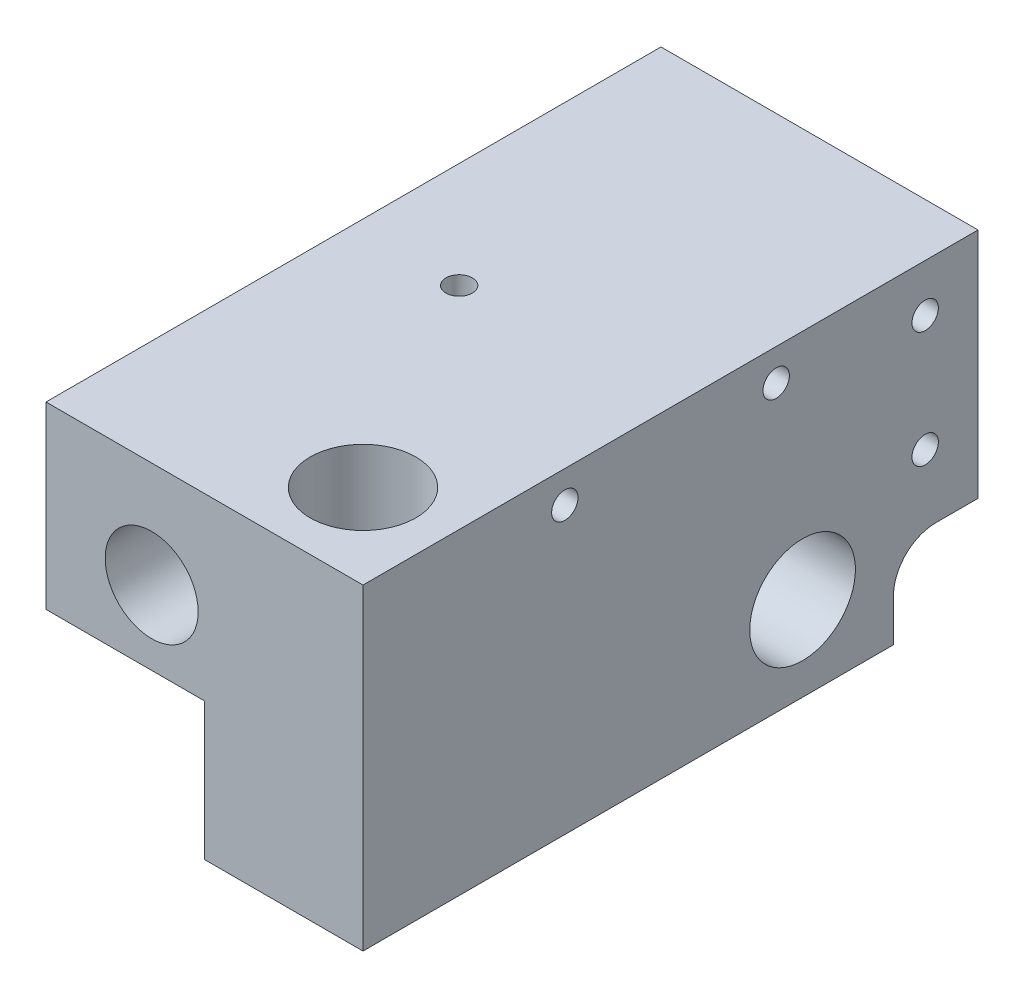
SolidWorks part; units mm, degrees
material "6061-T4 (SS)"
ref_plane "Piano frontale" through (0, 0, 0) normal (0, 0, 1) x (1, 0, 0)
ref_plane "Piano superiore" through (0, 0, 0) normal (0, 1, 0) x (1, 0, 0)
ref_plane "Piano destro" through (0, 0, 0) normal (1, 0, 0) x (0, 0, -1)
sketch "Schizzo1" plane through (0, 0, 0) normal (0, 0, 1) x (1, 0, 0)
  line L1 (0, 0) -> (30, 0)
  line L2 (0, 0) -> (0, 30)
  line L3 (0, 30) -> (30, 30)
  line L4 (30, 0) -> (30, 30)
  dimension "D1" = 30
extrude "Estrusione-Estrusione1" add sketch "Schizzo1" along normal blind 58.2
sketch "Schizzo2" plane through (0, 0, 0) normal (0, -1, 0) x (1, 0, 0)
  line L1 (0, 58.2) -> (30, 58.2) construction
  line L3 (30, 58.2) -> (30, 0) construction
  circle A0 centre (22, 50.2) radius 5
  dimension "D1" = 10
  dimension "D3" = 3
  dimension "D2" = 3
extrude "Taglio-Estrusione1" cut sketch "Schizzo2" against normal up to next
ref_point "Punto1"
sketch "Schizzo3" plane through (0, 0, 0) normal (-1, 0, 0) x (0, 0, 1)
  line L0 (50.2, 0) -> (50.2, 8) construction
  line L1 (50.2, 8) -> (16.6, 8) construction
  line L2 (58.2, 30) -> (58.2, 0) construction
  line L3 (58.2, 0) -> (0, 0) construction
  circle A0 centre (16.6, 8) radius 5
  dimension "D1" = 10
  dimension "D3" = 3
  dimension "D2" = 33.6
  dimension "D4" = 41.6
extrude "Taglio-Estrusione2" cut sketch "Schizzo3" against normal up to next
sketch "Schizzo5" plane through (0, 0, 0) normal (0, 0, -1) x (-1, 0, 0)
  line L0 (0, 30) -> (-30, 0) construction
  line L3 (0, 30) -> (-30, 30) construction
  line L5 (0, 30) -> (0, 0) construction
  circle A1 centre (-10, 20) radius 3
  dimension "D1" = 10
  dimension "D2" = 10
  dimension "D4" = 6
hole_wizard "Foro filettato G1/8-1" positions "Schizzo3D1" profile "Schizzo8" tap size "G1/8" standard "BSI"
sketch3d "Schizzo3D1"
  line L1 (30, 30, 58.2) -> (0, 30, 58.2) construction
  line L2 (0, 30, 58.2) -> (0, 0, 58.2) construction
  point P0 (10, 20, 58.2)
  dimension "D1" = 10
  dimension "D2" = 10
sketch "Schizzo8" plane through (10, 20, 58.2) normal (1, 0, 0) x (0, -1, 0)
  line L0 (0, 0) -> (0, 12.6438)
  line L1 (0, 12.6438) -> (4.4, 10)
  line L2 (4.4, 10) -> (4.4, 0)
  line L5 (4.4, 0) -> (0, 0)
  line L10 (0, 12.6438) -> (-4.4, 10) construction
  line L11 (0, -6.35) -> (0, 107.95) construction
  dimension "Tap Drill Dia." = 8.8
  dimension "Tap Drill Depth" = 10
  dimension "Drill Angle" = 118
sketch "Schizzo20" plane through (0, 0, 0) normal (-1, 0, 0) x (0, 0, 1)
  line L0 (4, 8) -> (0, 8)
  line L1 (0, 0) -> (8, 0) construction
  line L2 (0, 0) -> (0, 8) construction
  line L3 (0, 8) -> (8, 8) construction
  line L4 (8, 0) -> (8, 8) construction
  line L5 (0, 8) -> (0, 0)
  line L6 (0, 0) -> (8, 0)
  line L7 (8, 0) -> (8, 4)
  arc A1 (8, 4) -> (4, 8) centre (4, 4) ccw
  dimension "D1" = 8
  dimension "D2" = 8
  dimension "D3" = 8
extrude "Taglio-Estrusione5" cut sketch "Schizzo20" against normal blind 10
sketch "Schizzo21" plane through (30, 0, 0) normal (1, 0, 0) x (0, 0, -1)
  line L0 (-8, 0) -> (-8, 4) construction
  line L2 (-4, 8) -> (0, 8) construction
  line L3 (0, 8) -> (0, 0) construction
  line L4 (-8, 0) -> (-8, 4)
  line L5 (0, 0) -> (-8, 0)
  line L6 (-4, 8) -> (0, 8)
  line L7 (0, 8) -> (0, 0)
  arc A0 (-4, 8) -> (-8, 4) centre (-4, 4) ccw construction
  arc A1 (-4, 8) -> (-8, 4) centre (-4, 4) ccw
extrude "Taglio-Estrusione6" cut sketch "Schizzo21" against normal blind 10
sketch "Schizzo23" plane through (10, 0, 0) normal (-1, 0, 0) x (0, 0, 1)
  line L0 (0, 0) -> (8, 0) construction
  line L1 (0, 8) -> (0, 0) construction
  circle A0 centre (3, 3) radius 1.5
  point P2 (4, 0)
  dimension "D3" = 3
  dimension "D1" = 3
  dimension "D2" = 3
extrude "Taglio-Estrusione7" cut sketch "Schizzo23" against normal up to surface (10 mm away) up to face at (20, 4.1657, 4.1657)
sketch "Schizzo25" plane through (30, 0, 0) normal (1, 0, 0) x (0, 0, -1)
  line L0 (-58.2, 30) -> (0, 30) construction
  line L1 (0, 8) -> (0, 30) construction
  line L2 (-58.2, 0) -> (-58.2, 30) construction
  point P0 (-39.1, 27)
  point P1 (-19.1, 27)
  dimension "D1" = 3
  dimension "D2" = 19.1
  dimension "D3" = 39.1
hole_wizard "Foro filettato M3-2" positions "Schizzo3D2" profile "Schizzo27" tap size "M3" standard "ISO"
sketch3d "Schizzo3D2"
  point P0 (30, 27, 39.1)
  point P3 (30, 27, 19.1)
sketch "Schizzo27" plane through (30, 27, 39.1) normal (0, 1, 0) x (0, 0, -1)
  line L0 (0, 0) -> (0, 12.2511)
  line L1 (0, 12.2511) -> (1.25, 11.5)
  line L2 (1.25, 11.5) -> (1.25, 0)
  line L5 (1.25, 0) -> (0, 0)
  line L10 (0, 12.2511) -> (-1.25, 11.5) construction
  line L11 (0, -6.35) -> (0, 107.95) construction
  dimension "Tap Drill Dia." = 2.5
  dimension "Tap Drill Depth" = 11.5
  dimension "Drill Angle" = 118
cosmetic thread "Filettatura del foro2" parameters "D1"=10, "D2"=3
cosmetic thread "Filettatura del foro3" parameters "D1"=10, "D2"=3
sketch "Schizzo29" plane through (0, 0, 0) normal (-1, 0, 0) x (0, 0, 1)
  line L0 (20.2683, 0) -> (58.2, 0)
  line L1 (58.2, 0) -> (58.2, 13)
  line L2 (58.2, 13) -> (58.2, 0)
  line L5 (58.2, 0) -> (58.2, 30) construction
  line L7 (58.2, 0) -> (8, 0) construction
  line L8 (42.2, 13) -> (58.2, 13)
  arc A1 (42.2, 13) -> (20.2683, 0) centre (42.2, -12) ccw
  line M6 (8, 0) -> (58.2, 0)
  line M7 (58.2, 0) -> (58.2, 30)
  dimension "D3" = 25
  dimension "D1" = 16
  dimension "D2" = 12
extrude "Taglio-Estrusione11" cut sketch "Schizzo29" against normal blind 15 contours L8 A1 M6 M7 region at (0, 5.9257, 41.9996)
sketch "Schizzo30" plane through (0, 30, 0) normal (0, 1, 0) x (1, 0, 0)
  line L0 (10, 0) -> (10, -58.2) construction
  line L1 (30, 0) -> (0, 0) construction
  line L2 (30, -58.2) -> (30, 0) construction
  line L3 (0, -29.1) -> (30, -29.1) construction
  line L4 (0, -58.2) -> (0, 0) construction
  line L5 (30, -58.2) -> (0, -58.2) construction
  point P4 (10, -29.1)
  dimension "D1" = 20
  dimension "D2" = 29.1
hole_wizard "Foro filettato M3-3" positions "Schizzo3D4" profile "Schizzo31" tap size "M3" standard "DIN"
sketch3d "Schizzo3D4"
  point P0 (10, 30, 29.1)
  point P2 (10, 30, 29.1)
  point P4 (10, 30, 29.1)
  point P7 (10, 30, 29.1)
  point P9 (10, 30, 29.1)
sketch "Schizzo31" plane through (10, 30, 29.1) normal (1, 0, 0) x (0, 0, 1)
  line L0 (0, 0) -> (0, 5.7511)
  line L1 (0, 5.7511) -> (1.25, 5)
  line L2 (1.25, 5) -> (1.25, 0)
  line L5 (1.25, 0) -> (0, 0)
  line L10 (0, 5.7511) -> (-1.25, 5) construction
  line L11 (0, -6.35) -> (0, 107.95) construction
  dimension "Tap Drill Dia." = 2.5
  dimension "Tap Drill Depth" = 5
  dimension "Drill Angle" = 118
hole_wizard "Foro Ø16.0 (16)-1" positions "Schizzo3D5" profile "Schizzo32" hole size "Ø16.0" standard "ISO"
sketch3d "Schizzo3D5"
  point P0 (10, 20, 0)
sketch "Schizzo32" plane through (10, 20, 0) normal (1, 0, 0) x (0, 1, 0)
  line L0 (0, 0) -> (0, 16.8069)
  line L1 (0, 16.8069) -> (8, 12)
  line L2 (8, 12) -> (8, 0)
  line L5 (8, 0) -> (0, 0)
  line L10 (0, 16.8069) -> (-8, 12) construction
  line L11 (0, -6.35) -> (0, 107.95) construction
  dimension "Hole Dia." = 16
  dimension "Hole Depth" = 12
  dimension "Drill Angle" = 118
extrude "Taglio-Estrusione13" cut sketch "Schizzo5" against normal through all
sketch "Schizzo33" plane through (0, 0, 0) normal (-1, 0, 0) x (0, 0, 1)
  line L0 (12, 20) -> (0, 20) construction
  line L1 (12, 28) -> (12, 12) construction
  line L2 (0, 30) -> (0, 8) construction
  line L3 (58.2, 30) -> (0, 30) construction
  point P6 (5, 25.5)
  point P7 (5, 14.5)
  dimension "D1" = 5.5
  dimension "D2" = 7
  dimension "D3" = 4.5
  dimension "D4" = 15.5
  dimension "D5" = 5
hole_wizard "Foro filettato M3-4" positions "Schizzo3D6" profile "Schizzo34" tap size "M3" standard "ISO" end condition through all
sketch3d "Schizzo3D6"
  point P0 (0, 25.5, 5)
  point P3 (0, 14.5, 5)
sketch "Schizzo34" plane through (0, 25.5, 5) normal (0, 1, 0) x (0, 0, 1)
  line L0 (0, 0) -> (0, 30)
  line L1 (0, 30) -> (1.25, 30)
  line L2 (1.25, 30) -> (1.25, 0)
  line L5 (1.25, 0) -> (0, 0)
  line L11 (0, -6.35) -> (0, 107.95) construction
  dimension "Thread Major Dia." = 2.5
  dimension "Thru Tap Drill Depth" = 30
